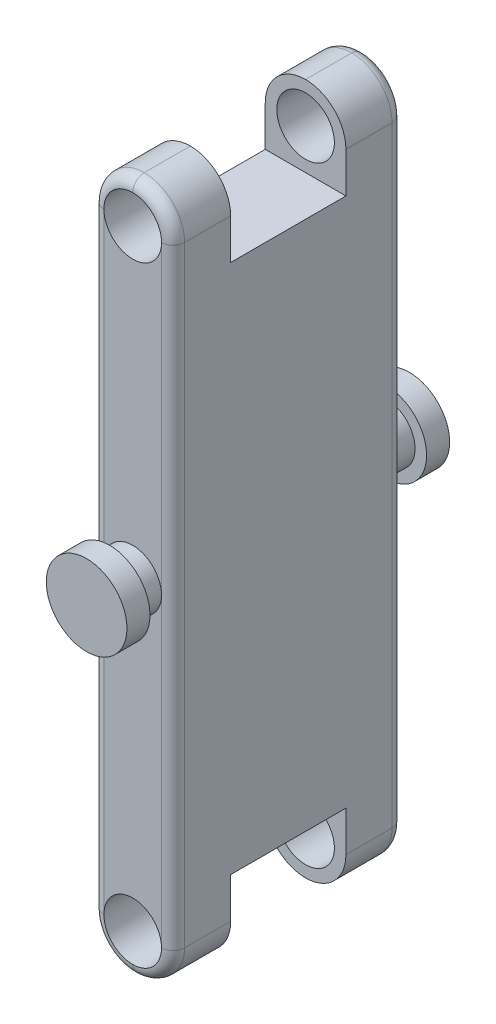
SolidWorks part; units mm, degrees
ref_plane "Front Plane" through (0, 0, 0) normal (0, 0, 1) x (1, 0, 0)
ref_plane "Top Plane" through (0, 0, 0) normal (0, 1, 0) x (1, 0, 0)
ref_plane "Right Plane" through (0, 0, 0) normal (1, 0, 0) x (0, 0, -1)
sketch "Sketch1" plane through (0, 0, 0) normal (0, 1, 0) x (1, 0, 0)
  line L1 (0, 0) -> (14, 0)
  line L2 (0, 0) -> (0, -20)
  line L3 (0, -20) -> (14, -20)
  line L4 (14, 0) -> (14, -20)
  dimension "D1" = 20
  dimension "D2" = 14
extrude "Boss-Extrude1" add sketch "Sketch1" along normal blind 120
sketch "Sketch2" plane through (0, 0, 0) normal (0, -1, 0) x (1, 0, 0)
  line L1 (14, 20) -> (14, 0) construction
  line L2 (0, 0) -> (14, 0)
  line L3 (0, 0) -> (0, 10)
  line L4 (0, 10) -> (14, 10)
  line L5 (14, 0) -> (14, 10)
  dimension "D1" = 10
extrude "Cut-Extrude1" cut sketch "Sketch2" against normal blind 14
sketch "Sketch4" plane through (0, 120, 0) normal (0, 1, 0) x (1, 0, 0)
  line L0 (14, -20) -> (14, 0) construction
  line L1 (0, 0) -> (14, 0)
  line L2 (0, 0) -> (0, -10)
  line L3 (0, -10) -> (14, -10)
  line L4 (14, 0) -> (14, -10)
  dimension "D1" = 10
sketch "Sketch5" plane through (0, 0, 10) normal (0, 0, -1) x (-1, 0, 0)
  circle A0 centre (-7, 7) radius 5
  dimension "D1" = 10
extrude "Cut-Extrude4" cut sketch "Sketch5" against normal blind 10
extrude "Cut-Extrude3" cut sketch "Sketch4" against normal blind 14
sketch "Sketch6" plane through (0, 0, 10) normal (0, 0, -1) x (-1, 0, 0)
  circle A0 centre (-7, 113) radius 5
  dimension "D1" = 10
extrude "Cut-Extrude5" cut sketch "Sketch6" against normal blind 10
mirror "Mirror1" about plane through (0, 120, 0) normal (0, 0, 1) of "Cut-Extrude5", "Cut-Extrude3", "Cut-Extrude4", "Cut-Extrude1", "Boss-Extrude1"
fillet "Fillet3" radius 7 8 edges at (0, 120, -15) (14, 120, -15) (0, 120, 15) (14, 120, 15) (0, 0, -15) (14, 0, -15) (0, 0, 15) (14, 0, 15)
sketch "Sketch7" plane through (0, 0, 20) normal (0, 0, 1) x (1, 0, 0)
  circle A0 centre (7, 60) radius 5
  dimension "D1" = 10
extrude "Boss-Extrude2" add sketch "Sketch7" along normal blind 4
sketch "Sketch8" plane through (0, 0, 24) normal (0, 0, 1) x (1, 0, 0)
  circle A0 centre (7, 60) radius 7
  dimension "D1" = 14
extrude "Boss-Extrude3" add sketch "Sketch8" along normal blind 4
mirror "Mirror2" about plane through (0, 0, 0) normal (0, 0, 1) of "Boss-Extrude3", "Boss-Extrude2"
fillet "Fillet4" radius 2 12 edges at (2.0503, 117.9497, 20) (11.9497, 117.9497, 20) (14, 60, 20) (11.9497, 2.0503, 20) (2.0503, 2.0503, 20) (2.0503, 117.9497, -20) (11.9497, 117.9497, -20) (14, 60, -20) (11.9497, 2.0503, -20) (2.0503, 2.0503, -20) (0, 60, 20) (0, 60, -20)
